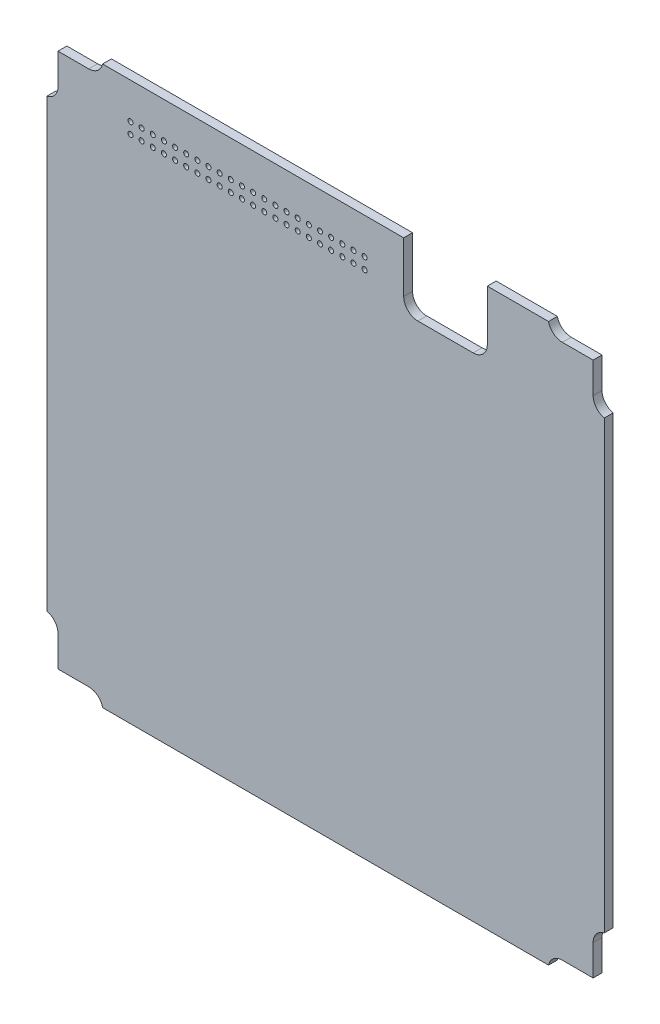
SolidWorks part; units mm, degrees
ref_plane "Front Plane" through (0, 0, 0) normal (0, 0, 1) x (1, 0, 0)
ref_plane "Top Plane" through (0, 0, 0) normal (0, 1, 0) x (1, 0, 0)
ref_plane "Right Plane" through (0, 0, 0) normal (1, 0, 0) x (0, 0, -1)
sketch "Sketch1" plane through (0, 0, 0) normal (0, 0, 1) x (1, 0, 0)
  line L0 (-40, 50) -> (-40, 48)
  line L1 (-50, -50) -> (50, -50)
  line L2 (-50, -50) -> (-50, 50)
  line L3 (-50, 50) -> (50, 50)
  line L4 (50, -50) -> (50, 50)
  line L5 (-50, -50) -> (50, 50) construction
  line L6 (-50, 50) -> (50, -50) construction
  line L7 (-50, 50) -> (-40, 50)
  line L8 (-50, 50) -> (-50, 40)
  line L9 (-40, 48) -> (-48, 48)
  line L10 (-48, 48) -> (-48, 40)
  line L11 (50, 50) -> (40, 50)
  line L12 (50, 50) -> (50, 40)
  line L13 (-48, 40) -> (-50, 40)
  line L14 (50, 40) -> (48, 40)
  line L15 (-50, -50) -> (-37.8649, -50)
  line L16 (-50, -50) -> (-50, -37.8649)
  line L17 (50, 50) -> (50, 40)
  line L18 (50, 50) -> (40, 50)
  line L19 (50, -50) -> (41.5, -50)
  line L20 (50, -50) -> (50, -41.5)
  line L21 (48, 40) -> (48, 48)
  line L22 (48, 48) -> (40, 48)
  line L23 (40, 48) -> (40, 50)
  line L24 (40, -50) -> (40, -48)
  line L25 (50, -50) -> (40, -50)
  line L26 (50, -50) -> (50, -40)
  line L27 (40, -48) -> (48, -48)
  line L28 (48, -48) -> (48, -40)
  line L29 (48, -40) -> (50, -40)
  line L30 (-50, -40) -> (-48, -40)
  line L31 (-50, -50) -> (-50, -40)
  line L32 (-50, -50) -> (-40, -50)
  line L33 (-48, -40) -> (-48, -48)
  line L34 (-48, -48) -> (-40, -48)
  line L35 (-40, -48) -> (-40, -50)
  point P0 (0, 0)
  point P38 (0, 0)
  dimension "D1" = 100
  dimension "D2" = 100
  dimension "D3" = 2
  dimension "D4" = 10
  dimension "D5" = 4
extrude "Boss-Extrude1" add sketch "Sketch1" along normal blind 1.5875 contours L1 L4 L3 L2 region at (0, 0, 0)
fillet "Fillet1" radius 2.54 8 edges at (-48, -40, 0.7937) (-40, -48, 0.7937) (40, -48, 0.7937) (48, -40, 0.7937) (48, 40, 0.7937) (40, 48, 0.7937) (-40, 48, 0.7937) (-48, 40, 0.7937)
sketch "Sketch2" plane through (0, 0, 1.5875) normal (0, 0, 1) x (1, 0, 0)
  line L0 (0, 50) -> (0, -50) construction
  line L1 (-40, 50) -> (40, 50) construction
  line L2 (-40, -50) -> (40, -50) construction
  line L4 (-36, 45.8) -> (8, 45.8) construction
  line L5 (-36, 45.8) -> (-36, 43.55) construction
  line L6 (-36, 43.55) -> (8, 43.55) construction
  line L7 (8, 45.8) -> (8, 43.55) construction
  line L8 (-36, 50) -> (8, 50) construction
  line L9 (-36, 50) -> (-36, 45.8) construction
  line L10 (-36, 45.8) -> (8, 45.8) construction
  line L11 (8, 50) -> (8, 45.8) construction
  circle A0 centre (-35, 43.55) radius 0.45
  circle A1 centre (-33, 43.55) radius 0.45
  circle A2 centre (-31, 43.55) radius 0.45
  circle A3 centre (-29, 43.55) radius 0.45
  circle A4 centre (-27, 43.55) radius 0.45
  circle A5 centre (-25, 43.55) radius 0.45
  circle A6 centre (-23, 43.55) radius 0.45
  circle A7 centre (-21, 43.55) radius 0.45
  circle A8 centre (-19, 43.55) radius 0.45
  circle A9 centre (-17, 43.55) radius 0.45
  circle A10 centre (-15, 43.55) radius 0.45
  circle A11 centre (-13, 43.55) radius 0.45
  circle A12 centre (-11, 43.55) radius 0.45
  circle A13 centre (-9, 43.55) radius 0.45
  circle A14 centre (-7, 43.55) radius 0.45
  circle A15 centre (-5, 43.55) radius 0.45
  circle A16 centre (-3, 43.55) radius 0.45
  circle A17 centre (-1, 43.55) radius 0.45
  circle A18 centre (1, 43.55) radius 0.45
  circle A19 centre (3, 43.55) radius 0.45
  circle A20 centre (5, 43.55) radius 0.45
  circle A21 centre (7, 43.55) radius 0.45
  circle A22 centre (-33, 41.55) radius 0.45
  circle A23 centre (-31, 41.55) radius 0.45
  circle A24 centre (-29, 41.55) radius 0.45
  circle A25 centre (-27, 41.55) radius 0.45
  circle A26 centre (-25, 41.55) radius 0.45
  circle A27 centre (-23, 41.55) radius 0.45
  circle A28 centre (-21, 41.55) radius 0.45
  circle A29 centre (-19, 41.55) radius 0.45
  circle A30 centre (-17, 41.55) radius 0.45
  circle A31 centre (-15, 41.55) radius 0.45
  circle A32 centre (-13, 41.55) radius 0.45
  circle A33 centre (-11, 41.55) radius 0.45
  circle A34 centre (-9, 41.55) radius 0.45
  circle A35 centre (-7, 41.55) radius 0.45
  circle A36 centre (-5, 41.55) radius 0.45
  circle A37 centre (-3, 41.55) radius 0.45
  circle A38 centre (-1, 41.55) radius 0.45
  circle A39 centre (1, 41.55) radius 0.45
  circle A40 centre (3, 41.55) radius 0.45
  circle A41 centre (5, 41.55) radius 0.45
  circle A42 centre (7, 41.55) radius 0.45
  circle A43 centre (-35, 41.55) radius 0.45
  dimension "D1" = 0.9
  dimension "D6" = 1
  dimension "D4" = 42
  dimension "D5" = 2
  dimension "D7" = 2.25
  dimension "D8" = 44
  dimension "D10" = 1
  dimension "D11" = 4.2
  dimension "D2" = 22
  dimension "D3" = 2
extrude "Cut-Extrude1" cut sketch "Sketch2" against normal through all
sketch "Sketch3" plane through (0, 50, 0) normal (0, 1, 0) x (1, 0, 0)
  line L0 (-40, 0) -> (40, 0) construction
  line L1 (14.0125, 0) -> (29.0125, 0)
  line L2 (14.0125, 0) -> (14.0125, -1.5875)
  line L3 (14.0125, -1.5875) -> (29.0125, -1.5875)
  line L4 (29.0125, 0) -> (29.0125, -1.5875)
  line L5 (-40, -1.5875) -> (40, -1.5875) construction
  line L6 (21.5125, 0) -> (21.5125, -1.5875) construction
  line L7 (16.725, 0) -> (16.725, -1.5875) construction
  line L8 (26.3, 0) -> (26.3, -1.5875) construction
  line L10 (7, 0) -> (7, -1.5875) construction
  line L11 (6.55, -1.5875) -> (7.45, -1.5875) construction
  dimension "D1" = 15
  dimension "D2" = 9.575
  dimension "D3" = 4.7875
  dimension "D4" = 9.725
extrude "Cut-Extrude2" cut sketch "Sketch3" against normal blind 11.652
fillet "Fillet2" radius 2.54 2 edges at (14.0125, 38.348, 0.7938) (29.0125, 38.348, 0.7937)
